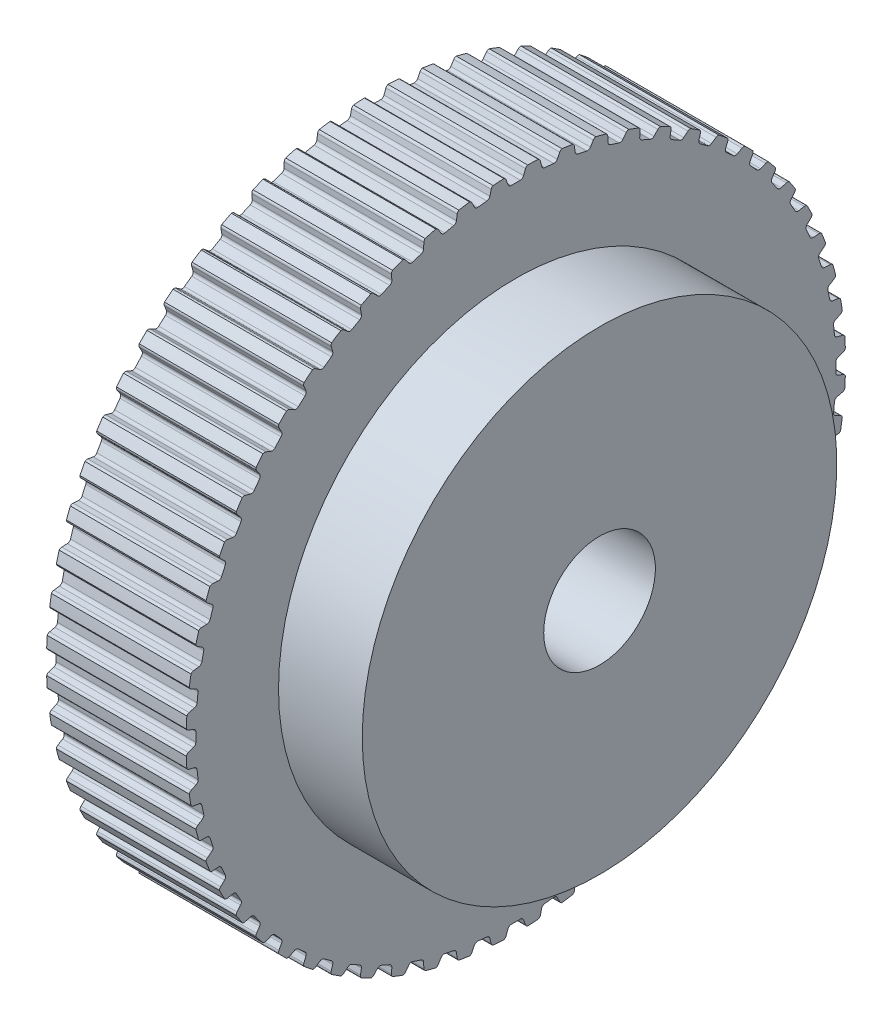
SolidWorks part; units mm, degrees
ref_plane "Plan de face" through (0, 0, 0) normal (0, 0, 1) x (1, 0, 0)
ref_plane "Plan de dessus" through (0, 0, 0) normal (0, 1, 0) x (1, 0, 0)
ref_plane "Plan de droite" through (0, 0, 0) normal (1, 0, 0) x (0, 0, -1)
ref_plane "Plane1" through (0, 0, 0) normal (-1, 0, 0) x (0, -1, 0)
sketch "Sketch1" plane through (0, 0, 0) normal (-1, 0, 0) x (0, -1, 0)
  line L0 (-23.4046, -1.7612) -> (-22.8517, -1.8991)
  line L1 (-22.8517, -1.8991) -> (-22.7472, -2.8936)
  line L2 (-22.7472, -2.8936) -> (-23.2593, -3.1434)
  line L3 (-23.0923, -4.198) -> (-22.528, -4.2773)
  line L4 (-22.528, -4.2773) -> (-22.3201, -5.2554)
  line L5 (-22.3201, -5.2554) -> (-22.8034, -5.5574)
  line L6 (-22.527, -6.5888) -> (-21.9575, -6.6087)
  line L7 (-21.9575, -6.6087) -> (-21.6485, -7.5597)
  line L8 (-21.6485, -7.5597) -> (-22.0975, -7.9106)
  line L9 (-21.7149, -8.9074) -> (-21.1464, -8.8677)
  line L10 (-21.1464, -8.8677) -> (-20.7397, -9.7812)
  line L11 (-20.7397, -9.7812) -> (-21.1496, -10.1771)
  line L12 (-20.6648, -11.1284) -> (-20.1036, -11.0295)
  line L13 (-20.1036, -11.0295) -> (-19.6036, -11.8955)
  line L14 (-19.6036, -11.8955) -> (-19.9699, -12.3321)
  line L15 (-19.3884, -13.2275) -> (-18.8406, -13.0705)
  line L16 (-18.8406, -13.0705) -> (-18.2528, -13.8795)
  line L17 (-18.2528, -13.8795) -> (-18.5715, -14.3519)
  line L18 (-17.8995, -15.1817) -> (-17.3712, -14.9682)
  line L19 (-17.3712, -14.9682) -> (-16.702, -15.7114)
  line L20 (-16.702, -15.7114) -> (-16.9696, -16.2146)
  line L21 (-16.2146, -16.9696) -> (-15.7114, -16.702)
  line L22 (-15.7114, -16.702) -> (-14.9682, -17.3712)
  line L23 (-14.9682, -17.3712) -> (-15.1817, -17.8995)
  line L24 (-14.3519, -18.5715) -> (-13.8795, -18.2528)
  line L25 (-13.8795, -18.2528) -> (-13.0705, -18.8406)
  line L26 (-13.0705, -18.8406) -> (-13.2275, -19.3884)
  line L27 (-12.3321, -19.9699) -> (-11.8955, -19.6036)
  line L28 (-11.8955, -19.6036) -> (-11.0295, -20.1036)
  line L29 (-11.0295, -20.1036) -> (-11.1284, -20.6648)
  line L30 (-10.1771, -21.1496) -> (-9.7812, -20.7397)
  line L31 (-9.7812, -20.7397) -> (-8.8677, -21.1464)
  line L32 (-8.8677, -21.1464) -> (-8.9074, -21.7149)
  line L33 (-7.9106, -22.0975) -> (-7.5597, -21.6485)
  line L34 (-7.5597, -21.6485) -> (-6.6087, -21.9575)
  line L35 (-6.6087, -21.9575) -> (-6.5888, -22.527)
  line L36 (-5.5574, -22.8034) -> (-5.2554, -22.3201)
  line L37 (-5.2554, -22.3201) -> (-4.2773, -22.528)
  line L38 (-4.2773, -22.528) -> (-4.198, -23.0923)
  line L39 (-3.1434, -23.2593) -> (-2.8936, -22.7472)
  line L40 (-2.8936, -22.7472) -> (-1.8991, -22.8517)
  line L41 (-1.8991, -22.8517) -> (-1.7612, -23.4046)
  line L42 (-0.6949, -23.4605) -> (-0.5, -22.925)
  line L43 (-0.5, -22.925) -> (0.5, -22.925)
  line L44 (0.5, -22.925) -> (0.6949, -23.4605)
  line L45 (1.7612, -23.4046) -> (1.8991, -22.8517)
  line L46 (1.8991, -22.8517) -> (2.8936, -22.7472)
  line L47 (2.8936, -22.7472) -> (3.1434, -23.2593)
  line L48 (4.198, -23.0923) -> (4.2773, -22.528)
  line L49 (4.2773, -22.528) -> (5.2554, -22.3201)
  line L50 (5.2554, -22.3201) -> (5.5574, -22.8034)
  line L51 (6.5888, -22.527) -> (6.6087, -21.9575)
  line L52 (6.6087, -21.9575) -> (7.5597, -21.6485)
  line L53 (7.5597, -21.6485) -> (7.9106, -22.0975)
  line L54 (8.9074, -21.7149) -> (8.8677, -21.1464)
  line L55 (8.8677, -21.1464) -> (9.7812, -20.7397)
  line L56 (9.7812, -20.7397) -> (10.1771, -21.1496)
  line L57 (11.1284, -20.6648) -> (11.0295, -20.1036)
  line L58 (11.0295, -20.1036) -> (11.8955, -19.6036)
  line L59 (11.8955, -19.6036) -> (12.3321, -19.9699)
  line L60 (13.2275, -19.3884) -> (13.0705, -18.8406)
  line L61 (13.0705, -18.8406) -> (13.8795, -18.2528)
  line L62 (13.8795, -18.2528) -> (14.3519, -18.5715)
  line L63 (15.1817, -17.8995) -> (14.9682, -17.3712)
  line L64 (14.9682, -17.3712) -> (15.7114, -16.702)
  line L65 (15.7114, -16.702) -> (16.2146, -16.9696)
  line L66 (16.9696, -16.2146) -> (16.702, -15.7114)
  line L67 (16.702, -15.7114) -> (17.3712, -14.9682)
  line L68 (17.3712, -14.9682) -> (17.8995, -15.1817)
  line L69 (18.5715, -14.3519) -> (18.2528, -13.8795)
  line L70 (18.2528, -13.8795) -> (18.8406, -13.0705)
  line L71 (18.8406, -13.0705) -> (19.3884, -13.2275)
  line L72 (19.9699, -12.3321) -> (19.6036, -11.8955)
  line L73 (19.6036, -11.8955) -> (20.1036, -11.0295)
  line L74 (20.1036, -11.0295) -> (20.6648, -11.1284)
  line L75 (21.1496, -10.1771) -> (20.7397, -9.7812)
  line L76 (20.7397, -9.7812) -> (21.1464, -8.8677)
  line L77 (21.1464, -8.8677) -> (21.7149, -8.9074)
  line L78 (22.0975, -7.9106) -> (21.6485, -7.5597)
  line L79 (21.6485, -7.5597) -> (21.9575, -6.6087)
  line L80 (21.9575, -6.6087) -> (22.527, -6.5888)
  line L81 (22.8034, -5.5574) -> (22.3201, -5.2554)
  line L82 (22.3201, -5.2554) -> (22.528, -4.2773)
  line L83 (22.528, -4.2773) -> (23.0923, -4.198)
  line L84 (23.2593, -3.1434) -> (22.7472, -2.8936)
  line L85 (22.7472, -2.8936) -> (22.8517, -1.8991)
  line L86 (22.8517, -1.8991) -> (23.4046, -1.7612)
  line L87 (23.4605, -0.6949) -> (22.925, -0.5)
  line L88 (22.925, -0.5) -> (22.925, 0.5)
  line L89 (22.925, 0.5) -> (23.4605, 0.6949)
  line L90 (23.4046, 1.7612) -> (22.8517, 1.8991)
  line L91 (22.8517, 1.8991) -> (22.7472, 2.8936)
  line L92 (22.7472, 2.8936) -> (23.2593, 3.1434)
  line L93 (23.0923, 4.198) -> (22.528, 4.2773)
  line L94 (22.528, 4.2773) -> (22.3201, 5.2554)
  line L95 (22.3201, 5.2554) -> (22.8034, 5.5574)
  line L96 (22.527, 6.5888) -> (21.9575, 6.6087)
  line L97 (21.9575, 6.6087) -> (21.6485, 7.5597)
  line L98 (21.6485, 7.5597) -> (22.0975, 7.9106)
  line L99 (21.7149, 8.9074) -> (21.1464, 8.8677)
  line L100 (21.1464, 8.8677) -> (20.7397, 9.7812)
  line L101 (20.7397, 9.7812) -> (21.1496, 10.1771)
  line L102 (20.6648, 11.1284) -> (20.1036, 11.0295)
  line L103 (20.1036, 11.0295) -> (19.6036, 11.8955)
  line L104 (19.6036, 11.8955) -> (19.9699, 12.3321)
  line L105 (19.3884, 13.2275) -> (18.8406, 13.0705)
  line L106 (18.8406, 13.0705) -> (18.2528, 13.8795)
  line L107 (18.2528, 13.8795) -> (18.5715, 14.3519)
  line L108 (17.8995, 15.1817) -> (17.3712, 14.9682)
  line L109 (17.3712, 14.9682) -> (16.702, 15.7114)
  line L110 (16.702, 15.7114) -> (16.9696, 16.2146)
  line L111 (16.2146, 16.9696) -> (15.7114, 16.702)
  line L112 (15.7114, 16.702) -> (14.9682, 17.3712)
  line L113 (14.9682, 17.3712) -> (15.1817, 17.8995)
  line L114 (14.3519, 18.5715) -> (13.8795, 18.2528)
  line L115 (13.8795, 18.2528) -> (13.0705, 18.8406)
  line L116 (13.0705, 18.8406) -> (13.2275, 19.3884)
  line L117 (12.3321, 19.9699) -> (11.8955, 19.6036)
  line L118 (11.8955, 19.6036) -> (11.0295, 20.1036)
  line L119 (11.0295, 20.1036) -> (11.1284, 20.6648)
  line L120 (10.1771, 21.1496) -> (9.7812, 20.7397)
  line L121 (9.7812, 20.7397) -> (8.8677, 21.1464)
  line L122 (8.8677, 21.1464) -> (8.9074, 21.7149)
  line L123 (7.9106, 22.0975) -> (7.5597, 21.6485)
  line L124 (7.5597, 21.6485) -> (6.6087, 21.9575)
  line L125 (6.6087, 21.9575) -> (6.5888, 22.527)
  line L126 (5.5574, 22.8034) -> (5.2554, 22.3201)
  line L127 (5.2554, 22.3201) -> (4.2773, 22.528)
  line L128 (4.2773, 22.528) -> (4.198, 23.0923)
  line L129 (3.1434, 23.2593) -> (2.8936, 22.7472)
  line L130 (2.8936, 22.7472) -> (1.8991, 22.8517)
  line L131 (1.8991, 22.8517) -> (1.7612, 23.4046)
  line L132 (0.6949, 23.4605) -> (0.5, 22.925)
  line L133 (0.5, 22.925) -> (-0.5, 22.925)
  line L134 (-0.5, 22.925) -> (-0.6949, 23.4605)
  line L135 (-1.7612, 23.4046) -> (-1.8991, 22.8517)
  line L136 (-1.8991, 22.8517) -> (-2.8936, 22.7472)
  line L137 (-2.8936, 22.7472) -> (-3.1434, 23.2593)
  line L138 (-4.198, 23.0923) -> (-4.2773, 22.528)
  line L139 (-4.2773, 22.528) -> (-5.2554, 22.3201)
  line L140 (-5.2554, 22.3201) -> (-5.5574, 22.8034)
  line L141 (-6.5888, 22.527) -> (-6.6087, 21.9575)
  line L142 (-6.6087, 21.9575) -> (-7.5597, 21.6485)
  line L143 (-7.5597, 21.6485) -> (-7.9106, 22.0975)
  line L144 (-8.9074, 21.7149) -> (-8.8677, 21.1464)
  line L145 (-8.8677, 21.1464) -> (-9.7812, 20.7397)
  line L146 (-9.7812, 20.7397) -> (-10.1771, 21.1496)
  line L147 (-11.1284, 20.6648) -> (-11.0295, 20.1036)
  line L148 (-11.0295, 20.1036) -> (-11.8955, 19.6036)
  line L149 (-11.8955, 19.6036) -> (-12.3321, 19.9699)
  line L150 (-13.2275, 19.3884) -> (-13.0705, 18.8406)
  line L151 (-13.0705, 18.8406) -> (-13.8795, 18.2528)
  line L152 (-13.8795, 18.2528) -> (-14.3519, 18.5715)
  line L153 (-15.1817, 17.8995) -> (-14.9682, 17.3712)
  line L154 (-14.9682, 17.3712) -> (-15.7114, 16.702)
  line L155 (-15.7114, 16.702) -> (-16.2146, 16.9696)
  line L156 (-16.9696, 16.2146) -> (-16.702, 15.7114)
  line L157 (-16.702, 15.7114) -> (-17.3712, 14.9682)
  line L158 (-17.3712, 14.9682) -> (-17.8995, 15.1817)
  line L159 (-18.5715, 14.3519) -> (-18.2528, 13.8795)
  line L160 (-18.2528, 13.8795) -> (-18.8406, 13.0705)
  line L161 (-18.8406, 13.0705) -> (-19.3884, 13.2275)
  line L162 (-19.9699, 12.3321) -> (-19.6036, 11.8955)
  line L163 (-19.6036, 11.8955) -> (-20.1036, 11.0295)
  line L164 (-20.1036, 11.0295) -> (-20.6648, 11.1284)
  line L165 (-21.1496, 10.1771) -> (-20.7397, 9.7812)
  line L166 (-20.7397, 9.7812) -> (-21.1464, 8.8677)
  line L167 (-21.1464, 8.8677) -> (-21.7149, 8.9074)
  line L168 (-22.0975, 7.9106) -> (-21.6485, 7.5597)
  line L169 (-21.6485, 7.5597) -> (-21.9575, 6.6087)
  line L170 (-21.9575, 6.6087) -> (-22.527, 6.5888)
  line L171 (-22.8034, 5.5574) -> (-22.3201, 5.2554)
  line L172 (-22.3201, 5.2554) -> (-22.528, 4.2773)
  line L173 (-22.528, 4.2773) -> (-23.0923, 4.198)
  line L174 (-23.2593, 3.1434) -> (-22.7472, 2.8936)
  line L175 (-22.7472, 2.8936) -> (-22.8517, 1.8991)
  line L176 (-22.8517, 1.8991) -> (-23.4046, 1.7612)
  line L177 (-23.4605, 0.6949) -> (-22.925, 0.5)
  line L178 (-22.925, 0.5) -> (-22.925, -0.5)
  line L179 (-22.925, -0.5) -> (-23.4605, -0.6949)
  arc A0 (-23.6099, -0.8443) -> (-23.5688, -1.6282) centre (0, 0) ccw
  arc A1 (-23.5688, -1.6282) -> (-23.4046, -1.7612) centre (-23.3441, -1.5186) ccw
  arc A2 (-23.2593, -3.1434) -> (-23.3923, -3.3076) centre (-23.1498, -3.3681) ccw
  arc A3 (-23.3923, -3.3076) -> (-23.2695, -4.0829) centre (0, 0) ccw
  arc A4 (-23.2695, -4.0829) -> (-23.0923, -4.198) centre (-23.0575, -3.9504) ccw
  arc A5 (-22.8034, -5.5574) -> (-22.9184, -5.7346) centre (-22.6709, -5.7694) ccw
  arc A6 (-22.9184, -5.7346) -> (-22.7153, -6.4929) centre (0, 0) ccw
  arc A7 (-22.7153, -6.4929) -> (-22.527, -6.5888) centre (-22.5183, -6.339) ccw
  arc A8 (-22.0975, -7.9106) -> (-22.1935, -8.0988) centre (-21.9436, -8.1076) ccw
  arc A9 (-22.1935, -8.0988) -> (-21.9121, -8.8317) centre (0, 0) ccw
  arc A10 (-21.9121, -8.8317) -> (-21.7149, -8.9074) centre (-21.7323, -8.658) ccw
  arc A11 (-21.1496, -10.1771) -> (-21.2253, -10.3743) centre (-20.9759, -10.3569) ccw
  arc A12 (-21.2253, -10.3743) -> (-20.8689, -11.0738) centre (0, 0) ccw
  arc A13 (-20.8689, -11.0738) -> (-20.6648, -11.1284) centre (-20.7083, -10.8822) ccw
  arc A14 (-19.9699, -12.3321) -> (-20.0246, -12.5361) centre (-19.7784, -12.4928) ccw
  arc A15 (-20.0246, -12.5361) -> (-19.5971, -13.1945) centre (0, 0) ccw
  arc A16 (-19.5971, -13.1945) -> (-19.3884, -13.2275) centre (-19.4573, -12.9872) ccw
  arc A17 (-18.5715, -14.3519) -> (-18.6046, -14.5606) centre (-18.3642, -14.4917) ccw
  arc A18 (-18.6046, -14.5606) -> (-18.1105, -15.1707) centre (0, 0) ccw
  arc A19 (-18.1105, -15.1707) -> (-17.8995, -15.1817) centre (-17.9932, -14.9499) ccw
  arc A20 (-16.9696, -16.2146) -> (-16.9806, -16.4255) centre (-16.7488, -16.3319) ccw
  arc A21 (-16.9806, -16.4255) -> (-16.4255, -16.9806) centre (0, 0) ccw
  arc A22 (-16.4255, -16.9806) -> (-16.2146, -16.9696) centre (-16.3319, -16.7488) ccw
  arc A23 (-15.1817, -17.8995) -> (-15.1707, -18.1105) centre (-14.9499, -17.9932) ccw
  arc A24 (-15.1707, -18.1105) -> (-14.5606, -18.6046) centre (0, 0) ccw
  arc A25 (-14.5606, -18.6046) -> (-14.3519, -18.5715) centre (-14.4917, -18.3642) ccw
  arc A26 (-13.2275, -19.3884) -> (-13.1945, -19.5971) centre (-12.9872, -19.4573) ccw
  arc A27 (-13.1945, -19.5971) -> (-12.5361, -20.0246) centre (0, 0) ccw
  arc A28 (-12.5361, -20.0246) -> (-12.3321, -19.9699) centre (-12.4928, -19.7784) ccw
  arc A29 (-11.1284, -20.6648) -> (-11.0738, -20.8689) centre (-10.8822, -20.7083) ccw
  arc A30 (-11.0738, -20.8689) -> (-10.3743, -21.2253) centre (0, 0) ccw
  arc A31 (-10.3743, -21.2253) -> (-10.1771, -21.1496) centre (-10.3569, -20.9759) ccw
  arc A32 (-8.9074, -21.7149) -> (-8.8317, -21.9121) centre (-8.658, -21.7323) ccw
  arc A33 (-8.8317, -21.9121) -> (-8.0988, -22.1935) centre (0, 0) ccw
  arc A34 (-8.0988, -22.1935) -> (-7.9106, -22.0975) centre (-8.1076, -21.9436) ccw
  arc A35 (-6.5888, -22.527) -> (-6.4929, -22.7153) centre (-6.339, -22.5183) ccw
  arc A36 (-6.4929, -22.7153) -> (-5.7346, -22.9184) centre (0, 0) ccw
  arc A37 (-5.7346, -22.9184) -> (-5.5574, -22.8034) centre (-5.7694, -22.6709) ccw
  arc A38 (-4.198, -23.0923) -> (-4.0829, -23.2695) centre (-3.9504, -23.0575) ccw
  arc A39 (-4.0829, -23.2695) -> (-3.3076, -23.3923) centre (0, 0) ccw
  arc A40 (-3.3076, -23.3923) -> (-3.1434, -23.2593) centre (-3.3681, -23.1498) ccw
  arc A41 (-1.7612, -23.4046) -> (-1.6282, -23.5688) centre (-1.5186, -23.3441) ccw
  arc A42 (-1.6282, -23.5688) -> (-0.8443, -23.6099) centre (0, 0) ccw
  arc A43 (-0.8443, -23.6099) -> (-0.6949, -23.4605) centre (-0.9298, -23.375) ccw
  arc A44 (0.6949, -23.4605) -> (0.8443, -23.6099) centre (0.9298, -23.375) ccw
  arc A45 (0.8443, -23.6099) -> (1.6282, -23.5688) centre (0, 0) ccw
  arc A46 (1.6282, -23.5688) -> (1.7612, -23.4046) centre (1.5186, -23.3441) ccw
  arc A47 (3.1434, -23.2593) -> (3.3076, -23.3923) centre (3.3681, -23.1498) ccw
  arc A48 (3.3076, -23.3923) -> (4.0829, -23.2695) centre (0, 0) ccw
  arc A49 (4.0829, -23.2695) -> (4.198, -23.0923) centre (3.9504, -23.0575) ccw
  arc A50 (5.5574, -22.8034) -> (5.7346, -22.9184) centre (5.7694, -22.6709) ccw
  arc A51 (5.7346, -22.9184) -> (6.4929, -22.7153) centre (0, 0) ccw
  arc A52 (6.4929, -22.7153) -> (6.5888, -22.527) centre (6.339, -22.5183) ccw
  arc A53 (7.9106, -22.0975) -> (8.0988, -22.1935) centre (8.1076, -21.9436) ccw
  arc A54 (8.0988, -22.1935) -> (8.8317, -21.9121) centre (0, 0) ccw
  arc A55 (8.8317, -21.9121) -> (8.9074, -21.7149) centre (8.658, -21.7323) ccw
  arc A56 (10.1771, -21.1496) -> (10.3743, -21.2253) centre (10.3569, -20.9759) ccw
  arc A57 (10.3743, -21.2253) -> (11.0738, -20.8689) centre (0, 0) ccw
  arc A58 (11.0738, -20.8689) -> (11.1284, -20.6648) centre (10.8822, -20.7083) ccw
  arc A59 (12.3321, -19.9699) -> (12.5361, -20.0246) centre (12.4928, -19.7784) ccw
  arc A60 (12.5361, -20.0246) -> (13.1945, -19.5971) centre (0, 0) ccw
  arc A61 (13.1945, -19.5971) -> (13.2275, -19.3884) centre (12.9872, -19.4573) ccw
  arc A62 (14.3519, -18.5715) -> (14.5606, -18.6046) centre (14.4917, -18.3642) ccw
  arc A63 (14.5606, -18.6046) -> (15.1707, -18.1105) centre (0, 0) ccw
  arc A64 (15.1707, -18.1105) -> (15.1817, -17.8995) centre (14.9499, -17.9932) ccw
  arc A65 (16.2146, -16.9696) -> (16.4255, -16.9806) centre (16.3319, -16.7488) ccw
  arc A66 (16.4255, -16.9806) -> (16.9806, -16.4255) centre (0, 0) ccw
  arc A67 (16.9806, -16.4255) -> (16.9696, -16.2146) centre (16.7488, -16.3319) ccw
  arc A68 (17.8995, -15.1817) -> (18.1105, -15.1707) centre (17.9932, -14.9499) ccw
  arc A69 (18.1105, -15.1707) -> (18.6046, -14.5606) centre (0, 0) ccw
  arc A70 (18.6046, -14.5606) -> (18.5715, -14.3519) centre (18.3642, -14.4917) ccw
  arc A71 (19.3884, -13.2275) -> (19.5971, -13.1945) centre (19.4573, -12.9872) ccw
  arc A72 (19.5971, -13.1945) -> (20.0246, -12.5361) centre (0, 0) ccw
  arc A73 (20.0246, -12.5361) -> (19.9699, -12.3321) centre (19.7784, -12.4928) ccw
  arc A74 (20.6648, -11.1284) -> (20.8689, -11.0738) centre (20.7083, -10.8822) ccw
  arc A75 (20.8689, -11.0738) -> (21.2253, -10.3743) centre (0, 0) ccw
  arc A76 (21.2253, -10.3743) -> (21.1496, -10.1771) centre (20.9759, -10.3569) ccw
  arc A77 (21.7149, -8.9074) -> (21.9121, -8.8317) centre (21.7323, -8.658) ccw
  arc A78 (21.9121, -8.8317) -> (22.1935, -8.0988) centre (0, 0) ccw
  arc A79 (22.1935, -8.0988) -> (22.0975, -7.9106) centre (21.9436, -8.1076) ccw
  arc A80 (22.527, -6.5888) -> (22.7153, -6.4929) centre (22.5183, -6.339) ccw
  arc A81 (22.7153, -6.4929) -> (22.9184, -5.7346) centre (0, 0) ccw
  arc A82 (22.9184, -5.7346) -> (22.8034, -5.5574) centre (22.6709, -5.7694) ccw
  arc A83 (23.0923, -4.198) -> (23.2695, -4.0829) centre (23.0575, -3.9504) ccw
  arc A84 (23.2695, -4.0829) -> (23.3923, -3.3076) centre (0, 0) ccw
  arc A85 (23.3923, -3.3076) -> (23.2593, -3.1434) centre (23.1498, -3.3681) ccw
  arc A86 (23.4046, -1.7612) -> (23.5688, -1.6282) centre (23.3441, -1.5186) ccw
  arc A87 (23.5688, -1.6282) -> (23.6099, -0.8443) centre (0, 0) ccw
  arc A88 (23.6099, -0.8443) -> (23.4605, -0.6949) centre (23.375, -0.9298) ccw
  arc A89 (23.4605, 0.6949) -> (23.6099, 0.8443) centre (23.375, 0.9298) ccw
  arc A90 (23.6099, 0.8443) -> (23.5688, 1.6282) centre (0, 0) ccw
  arc A91 (23.5688, 1.6282) -> (23.4046, 1.7612) centre (23.3441, 1.5186) ccw
  arc A92 (23.2593, 3.1434) -> (23.3923, 3.3076) centre (23.1498, 3.3681) ccw
  arc A93 (23.3923, 3.3076) -> (23.2695, 4.0829) centre (0, 0) ccw
  arc A94 (23.2695, 4.0829) -> (23.0923, 4.198) centre (23.0575, 3.9504) ccw
  arc A95 (22.8034, 5.5574) -> (22.9184, 5.7346) centre (22.6709, 5.7694) ccw
  arc A96 (22.9184, 5.7346) -> (22.7153, 6.4929) centre (0, 0) ccw
  arc A97 (22.7153, 6.4929) -> (22.527, 6.5888) centre (22.5183, 6.339) ccw
  arc A98 (22.0975, 7.9106) -> (22.1935, 8.0988) centre (21.9436, 8.1076) ccw
  arc A99 (22.1935, 8.0988) -> (21.9121, 8.8317) centre (0, 0) ccw
  arc A100 (21.9121, 8.8317) -> (21.7149, 8.9074) centre (21.7323, 8.658) ccw
  arc A101 (21.1496, 10.1771) -> (21.2253, 10.3743) centre (20.9759, 10.3569) ccw
  arc A102 (21.2253, 10.3743) -> (20.8689, 11.0738) centre (0, 0) ccw
  arc A103 (20.8689, 11.0738) -> (20.6648, 11.1284) centre (20.7083, 10.8822) ccw
  arc A104 (19.9699, 12.3321) -> (20.0246, 12.5361) centre (19.7784, 12.4928) ccw
  arc A105 (20.0246, 12.5361) -> (19.5971, 13.1945) centre (0, 0) ccw
  arc A106 (19.5971, 13.1945) -> (19.3884, 13.2275) centre (19.4573, 12.9872) ccw
  arc A107 (18.5715, 14.3519) -> (18.6046, 14.5606) centre (18.3642, 14.4917) ccw
  arc A108 (18.6046, 14.5606) -> (18.1105, 15.1707) centre (0, 0) ccw
  arc A109 (18.1105, 15.1707) -> (17.8995, 15.1817) centre (17.9932, 14.9499) ccw
  arc A110 (16.9696, 16.2146) -> (16.9806, 16.4255) centre (16.7488, 16.3319) ccw
  arc A111 (16.9806, 16.4255) -> (16.4255, 16.9806) centre (0, 0) ccw
  arc A112 (16.4255, 16.9806) -> (16.2146, 16.9696) centre (16.3319, 16.7488) ccw
  arc A113 (15.1817, 17.8995) -> (15.1707, 18.1105) centre (14.9499, 17.9932) ccw
  arc A114 (15.1707, 18.1105) -> (14.5606, 18.6046) centre (0, 0) ccw
  arc A115 (14.5606, 18.6046) -> (14.3519, 18.5715) centre (14.4917, 18.3642) ccw
  arc A116 (13.2275, 19.3884) -> (13.1945, 19.5971) centre (12.9872, 19.4573) ccw
  arc A117 (13.1945, 19.5971) -> (12.5361, 20.0246) centre (0, 0) ccw
  arc A118 (12.5361, 20.0246) -> (12.3321, 19.9699) centre (12.4928, 19.7784) ccw
  arc A119 (11.1284, 20.6648) -> (11.0738, 20.8689) centre (10.8822, 20.7083) ccw
  arc A120 (11.0738, 20.8689) -> (10.3743, 21.2253) centre (0, 0) ccw
  arc A121 (10.3743, 21.2253) -> (10.1771, 21.1496) centre (10.3569, 20.9759) ccw
  arc A122 (8.9074, 21.7149) -> (8.8317, 21.9121) centre (8.658, 21.7323) ccw
  arc A123 (8.8317, 21.9121) -> (8.0988, 22.1935) centre (0, 0) ccw
  arc A124 (8.0988, 22.1935) -> (7.9106, 22.0975) centre (8.1076, 21.9436) ccw
  arc A125 (6.5888, 22.527) -> (6.4929, 22.7153) centre (6.339, 22.5183) ccw
  arc A126 (6.4929, 22.7153) -> (5.7346, 22.9184) centre (0, 0) ccw
  arc A127 (5.7346, 22.9184) -> (5.5574, 22.8034) centre (5.7694, 22.6709) ccw
  arc A128 (4.198, 23.0923) -> (4.0829, 23.2695) centre (3.9504, 23.0575) ccw
  arc A129 (4.0829, 23.2695) -> (3.3076, 23.3923) centre (0, 0) ccw
  arc A130 (3.3076, 23.3923) -> (3.1434, 23.2593) centre (3.3681, 23.1498) ccw
  arc A131 (1.7612, 23.4046) -> (1.6282, 23.5688) centre (1.5186, 23.3441) ccw
  arc A132 (1.6282, 23.5688) -> (0.8443, 23.6099) centre (0, 0) ccw
  arc A133 (0.8443, 23.6099) -> (0.6949, 23.4605) centre (0.9298, 23.375) ccw
  arc A134 (-0.6949, 23.4605) -> (-0.8443, 23.6099) centre (-0.9298, 23.375) ccw
  arc A135 (-0.8443, 23.6099) -> (-1.6282, 23.5688) centre (0, 0) ccw
  arc A136 (-1.6282, 23.5688) -> (-1.7612, 23.4046) centre (-1.5186, 23.3441) ccw
  arc A137 (-3.1434, 23.2593) -> (-3.3076, 23.3923) centre (-3.3681, 23.1498) ccw
  arc A138 (-3.3076, 23.3923) -> (-4.0829, 23.2695) centre (0, 0) ccw
  arc A139 (-4.0829, 23.2695) -> (-4.198, 23.0923) centre (-3.9504, 23.0575) ccw
  arc A140 (-5.5574, 22.8034) -> (-5.7346, 22.9184) centre (-5.7694, 22.6709) ccw
  arc A141 (-5.7346, 22.9184) -> (-6.4929, 22.7153) centre (0, 0) ccw
  arc A142 (-6.4929, 22.7153) -> (-6.5888, 22.527) centre (-6.339, 22.5183) ccw
  arc A143 (-7.9106, 22.0975) -> (-8.0988, 22.1935) centre (-8.1076, 21.9436) ccw
  arc A144 (-8.0988, 22.1935) -> (-8.8317, 21.9121) centre (0, 0) ccw
  arc A145 (-8.8317, 21.9121) -> (-8.9074, 21.7149) centre (-8.658, 21.7323) ccw
  arc A146 (-10.1771, 21.1496) -> (-10.3743, 21.2253) centre (-10.3569, 20.9759) ccw
  arc A147 (-10.3743, 21.2253) -> (-11.0738, 20.8689) centre (0, 0) ccw
  arc A148 (-11.0738, 20.8689) -> (-11.1284, 20.6648) centre (-10.8822, 20.7083) ccw
  arc A149 (-12.3321, 19.9699) -> (-12.5361, 20.0246) centre (-12.4928, 19.7784) ccw
  arc A150 (-12.5361, 20.0246) -> (-13.1945, 19.5971) centre (0, 0) ccw
  arc A151 (-13.1945, 19.5971) -> (-13.2275, 19.3884) centre (-12.9872, 19.4573) ccw
  arc A152 (-14.3519, 18.5715) -> (-14.5606, 18.6046) centre (-14.4917, 18.3642) ccw
  arc A153 (-14.5606, 18.6046) -> (-15.1707, 18.1105) centre (0, 0) ccw
  arc A154 (-15.1707, 18.1105) -> (-15.1817, 17.8995) centre (-14.9499, 17.9932) ccw
  arc A155 (-16.2146, 16.9696) -> (-16.4255, 16.9806) centre (-16.3319, 16.7488) ccw
  arc A156 (-16.4255, 16.9806) -> (-16.9806, 16.4255) centre (0, 0) ccw
  arc A157 (-16.9806, 16.4255) -> (-16.9696, 16.2146) centre (-16.7488, 16.3319) ccw
  arc A158 (-17.8995, 15.1817) -> (-18.1105, 15.1707) centre (-17.9932, 14.9499) ccw
  arc A159 (-18.1105, 15.1707) -> (-18.6046, 14.5606) centre (0, 0) ccw
  arc A160 (-18.6046, 14.5606) -> (-18.5715, 14.3519) centre (-18.3642, 14.4917) ccw
  arc A161 (-19.3884, 13.2275) -> (-19.5971, 13.1945) centre (-19.4573, 12.9872) ccw
  arc A162 (-19.5971, 13.1945) -> (-20.0246, 12.5361) centre (0, 0) ccw
  arc A163 (-20.0246, 12.5361) -> (-19.9699, 12.3321) centre (-19.7784, 12.4928) ccw
  arc A164 (-20.6648, 11.1284) -> (-20.8689, 11.0738) centre (-20.7083, 10.8822) ccw
  arc A165 (-20.8689, 11.0738) -> (-21.2253, 10.3743) centre (0, 0) ccw
  arc A166 (-21.2253, 10.3743) -> (-21.1496, 10.1771) centre (-20.9759, 10.3569) ccw
  arc A167 (-21.7149, 8.9074) -> (-21.9121, 8.8317) centre (-21.7323, 8.658) ccw
  arc A168 (-21.9121, 8.8317) -> (-22.1935, 8.0988) centre (0, 0) ccw
  arc A169 (-22.1935, 8.0988) -> (-22.0975, 7.9106) centre (-21.9436, 8.1076) ccw
  arc A170 (-22.527, 6.5888) -> (-22.7153, 6.4929) centre (-22.5183, 6.339) ccw
  arc A171 (-22.7153, 6.4929) -> (-22.9184, 5.7346) centre (0, 0) ccw
  arc A172 (-22.9184, 5.7346) -> (-22.8034, 5.5574) centre (-22.6709, 5.7694) ccw
  arc A173 (-23.0923, 4.198) -> (-23.2695, 4.0829) centre (-23.0575, 3.9504) ccw
  arc A174 (-23.2695, 4.0829) -> (-23.3923, 3.3076) centre (0, 0) ccw
  arc A175 (-23.3923, 3.3076) -> (-23.2593, 3.1434) centre (-23.1498, 3.3681) ccw
  arc A176 (-23.4046, 1.7612) -> (-23.5688, 1.6282) centre (-23.3441, 1.5186) ccw
  arc A177 (-23.5688, 1.6282) -> (-23.6099, 0.8443) centre (0, 0) ccw
  arc A178 (-23.6099, 0.8443) -> (-23.4605, 0.6949) centre (-23.375, 0.9298) ccw
  arc A179 (-23.4605, -0.6949) -> (-23.6099, -0.8443) centre (-23.375, -0.9298) ccw
extrude "Boss-Extrude1" add sketch "Sketch1" against normal blind 10
ref_plane "Plane2" through (0, 0, 0) normal (0, 0, -1) x (-1, 0, 0)
sketch "Sketch2" plane through (0, 0, 0) normal (0, 0, -1) x (-1, 0, 0)
  line L0 (-16, 17) -> (-16, 0)
  line L1 (-16, 0) -> (-10, 0)
  line L2 (-10, 0) -> (-10, 17)
  line L3 (-10, 17) -> (-16, 17)
  line L4 (-16, 0) -> (-10, 0) construction
revolve "Revolve1" add sketch "Sketch2" angle 360 about L4 reverse direction yes
hole_wizard "Ø8.0 (8) Diameter Hole1" positions "Sketch4" profile "Sketch3" hole size "Ø8.0" standard "ANSI Metric"
sketch "Sketch4" plane through (0, 0, 0) normal (-1, 0, 0) x (0, 0, 1)
  point P0 (0, 0)
sketch "Sketch3" plane through (0, 0, 0) normal (0, 1, 0) x (0, 0, 1)
  line L0 (0, 0) -> (0, 16)
  line L1 (0, 16) -> (4, 16)
  line L2 (4, 16) -> (4, 0)
  line L5 (4, 0) -> (0, 0)
  line L11 (0, -6.35) -> (0, 107.95) construction
  dimension "Thru Hole Dia." = 8
  dimension "Thru Hole Depth" = 16
fillet "Fillet1" radius 0.25 120 edges at (5, -22.8517, -1.8991) (5, 4.2773, -22.528) (5, -13.8795, -18.2528) (5, 19.6036, -11.8955) (5, 22.925, 0.5) (5, -20.1036, -11.0295) (5, 22.925, -0.5) (5, -5.2554, -22.3201) (5, 13.0705, -18.8406) (5, 22.7472, -2.8936) (5, 22.7472, 2.8936) (5, -21.9575, -6.6087) (5, 22.8517, 1.8991) (5, -17.3712, -14.9682) (5, -9.7812, -20.7397) (5, -0.5, -22.925) (5, 22.3201, 5.2554) (5, 8.8677, -21.1464) (5, 22.528, 4.2773) (5, 16.702, -15.7114) (5, 21.6485, -7.5597) (5, -22.925, 0.5) (5, 21.6485, 7.5597) (5, -22.528, -4.2773) (5, 21.9575, 6.6087) (5, -21.1464, -8.8677) (5, -18.8406, -13.0705) (5, -15.7114, -16.702) (5, 20.7397, 9.7812) (5, -11.8955, -19.6036) (5, 21.1464, 8.8677) (5, -7.5597, -21.6485) (5, -2.8936, -22.7472) (5, 1.8991, -22.8517) (5, 19.6036, 11.8955) (5, 6.6087, -21.9575) (5, 20.1036, 11.0295) (5, 11.0295, -20.1036) (5, 14.9682, -17.3712) (5, 18.2528, -13.8795) (5, 18.2528, 13.8795) (5, 20.7397, -9.7812) (5, 18.8406, 13.0705) (5, 22.3201, -5.2554) (5, 16.702, 15.7114) (5, 17.3712, 14.9682) (5, 14.9682, 17.3712) (5, 15.7114, 16.702) (5, 13.0705, 18.8406) (5, 13.8795, 18.2528) (5, 11.0295, 20.1036) (5, 11.8955, 19.6036) (5, 8.8677, 21.1464) (5, 9.7812, 20.7397) (5, 6.6087, 21.9575) (5, 7.5597, 21.6485) (5, 4.2773, 22.528) (5, 5.2554, 22.3201) (5, 1.8991, 22.8517) (5, 2.8936, 22.7472) (5, -22.925, -0.5) (5, -22.7472, -2.8936) (5, -0.5, 22.925) (5, 0.5, 22.925) (5, -22.3201, -5.2554) (5, -21.6485, -7.5597) (5, -2.8936, 22.7472) (5, -1.8991, 22.8517) (5, -20.7397, -9.7812) (5, -19.6036, -11.8955) (5, -5.2554, 22.3201) (5, -4.2773, 22.528) (5, -18.2528, -13.8795) (5, -16.702, -15.7114) (5, -7.5597, 21.6485) (5, -6.6087, 21.9575) (5, -14.9682, -17.3712) (5, -13.0705, -18.8406) (5, -9.7812, 20.7397) (5, -8.8677, 21.1464) (5, -11.0295, -20.1036) (5, -8.8677, -21.1464) (5, -11.8955, 19.6036) (5, -11.0295, 20.1036) (5, -6.6087, -21.9575) (5, -4.2773, -22.528) (5, -13.8795, 18.2528) (5, -13.0705, 18.8406) (5, -1.8991, -22.8517) (5, 0.5, -22.925) (5, -15.7114, 16.702) (5, -14.9682, 17.3712) (5, 2.8936, -22.7472) (5, 5.2554, -22.3201) (5, -17.3712, 14.9682) (5, -16.702, 15.7114) (5, 7.5597, -21.6485) (5, 9.7812, -20.7397) (5, -18.8406, 13.0705) (5, -18.2528, 13.8795) (5, 11.8955, -19.6036) (5, 13.8795, -18.2528) (5, -20.1036, 11.0295) (5, -19.6036, 11.8955) (5, 15.7114, -16.702) (5, 17.3712, -14.9682) (5, -21.1464, 8.8677) (5, -20.7397, 9.7812) (5, 18.8406, -13.0705) (5, 20.1036, -11.0295) (5, -21.9575, 6.6087) (5, -21.6485, 7.5597) (5, 21.1464, -8.8677) (5, 21.9575, -6.6087) (5, -22.528, 4.2773) (5, -22.3201, 5.2554) (5, 22.528, -4.2773) (5, 22.8517, -1.8991) (5, -22.8517, 1.8991) (5, -22.7472, 2.8936) tangent propagation no
